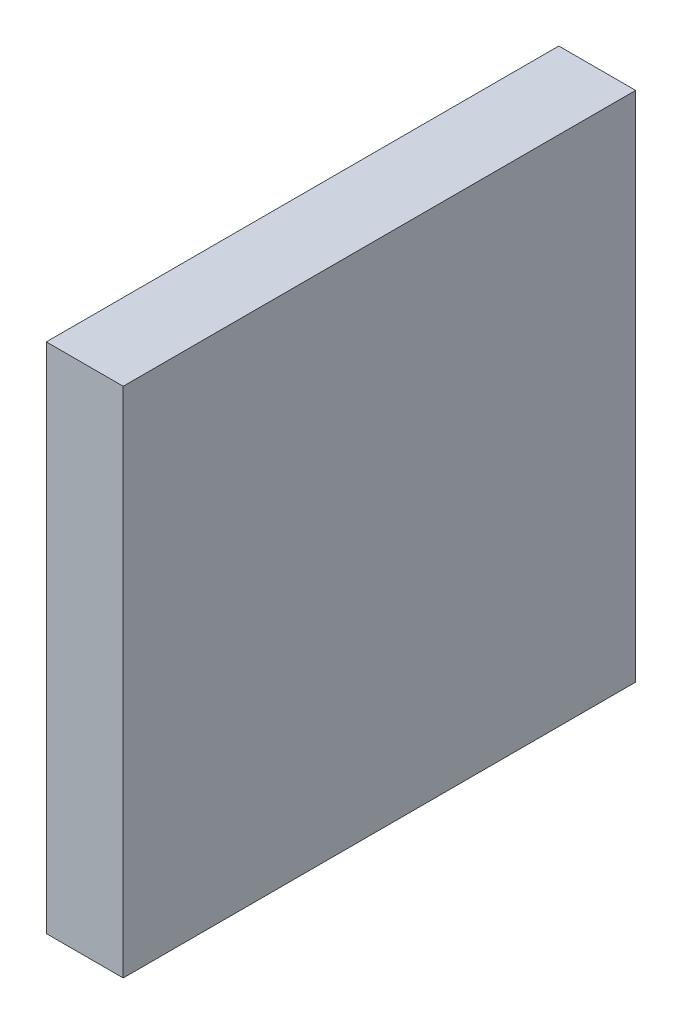
SolidWorks part; units mm, degrees
ref_plane "Ebene vorne" through (0, 0, 0) normal (0, 0, 1) x (1, 0, 0)
ref_plane "Ebene oben" through (0, 0, 0) normal (0, 1, 0) x (1, 0, 0)
ref_plane "Ebene rechts" through (0, 0, 0) normal (1, 0, 0) x (0, 0, -1)
sketch "Sketch2" plane through (0, 0, 0) normal (1, 0, 0) x (0, 0, -1)
  line L0 (-81.0651, 0) -> (92.8994, 0) construction
  line L1 (-50, 50) -> (50, 50)
  line L2 (-50, 50) -> (-50, -50)
  line L3 (-50, -50) -> (50, -50)
  line L4 (50, 50) -> (50, -50)
  line L5 (0, 88.4615) -> (0, -84.3195) construction
  dimension "D1" = 100
  dimension "D2" = 100
extrude "Boss-Extrude1" add sketch "Sketch2" along normal blind 15
